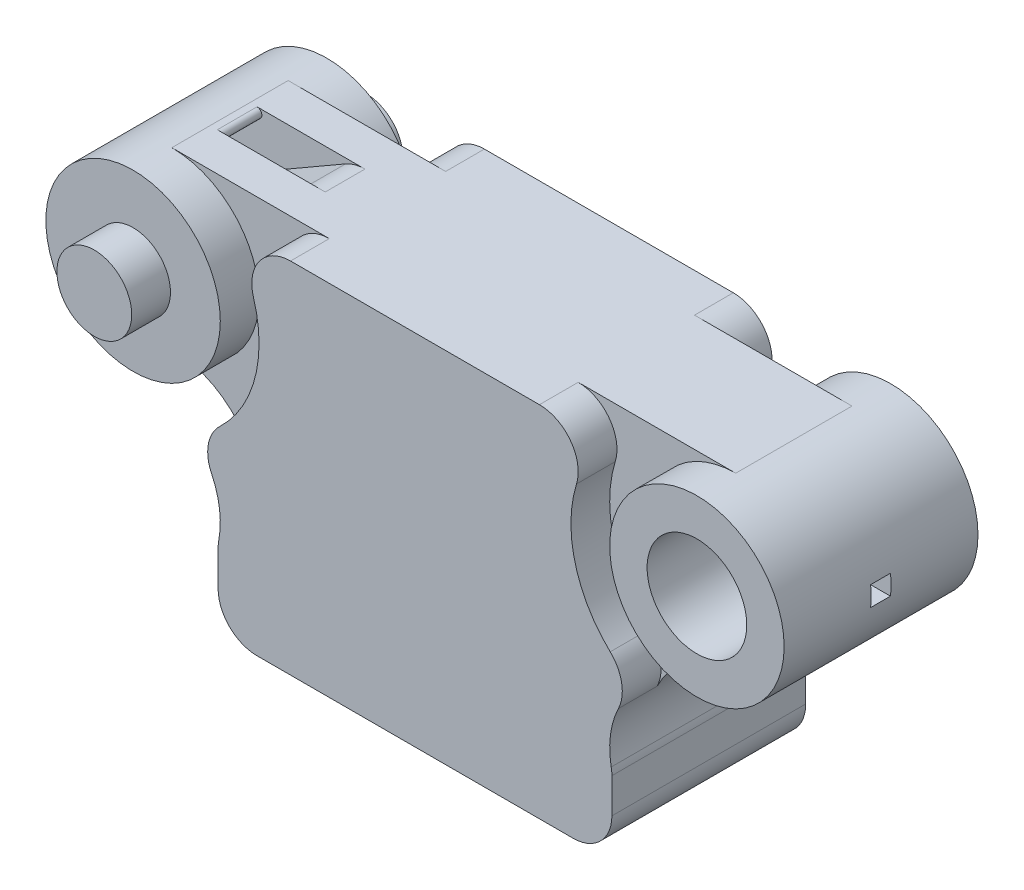
SolidWorks part; units mm, degrees
material "ABS"
ref_plane "Front Plane" through (0, 0, 0) normal (0, 0, 1) x (1, 0, 0)
ref_plane "Top Plane" through (0, 0, 0) normal (0, 1, 0) x (1, 0, 0)
ref_plane "Right Plane" through (0, 0, 0) normal (1, 0, 0) x (0, 0, -1)
sketch "Sketch1" plane through (0, 0, 0) normal (0, 0, 1) x (1, 0, 0)
  line L0 (5.5562, 0) -> (35.7188, 0)
  line L1 (0, 5.5562) -> (41.275, 5.5562)
  line L2 (0, 5.5562) -> (0, -5.5562) construction
  line L3 (0, -5.5562) -> (41.275, -5.5562) construction
  line L4 (41.275, 5.5562) -> (41.275, -5.5562) construction
  line L5 (0, 5.5562) -> (41.275, 5.5562) construction
  line L9 (0, 0) -> (9.0934, 0.7956) construction
  line L10 (41.275, 9.1281) -> (41.275, 0) construction
  line L11 (32.1816, 0.7956) -> (30.4025, 0.9512) construction
  line L12 (32.1816, 0.7956) -> (41.275, 0) construction
  line L13 (30.4025, 0.9512) -> (28.6233, 1.1069) construction
  circle A0 centre (0, 0) radius 5.5562 construction
  circle A1 centre (41.275, 0) radius 5.5562 construction
  arc A2 (0, 5.5562) -> (0, -5.5562) centre (0, 0) ccw
  arc A3 (41.275, -5.5562) -> (41.275, 5.5562) centre (41.275, 0) ccw
  circle A4 centre (0, 0) radius 1.7859
  circle A5 centre (41.275, 0) radius 1.7859
  arc A6 (0, -5.5562) -> (5.5562, 0) centre (0, 0) ccw
  arc A7 (35.7188, 0) -> (41.275, -5.5562) centre (41.275, 0) ccw
  circle A16 centre (41.275, -9.1281) radius 1.7859
  circle A20 centre (41.275, -9.1281) radius 3.5719
  circle A21 centre (32.1816, 0.7956) radius 1.7859
  circle A22 centre (32.1816, 0.7956) radius 3.5719 construction
  circle A23 centre (41.275, 0) radius 9.1281 construction
  circle A25 centre (0, 0) radius 9.1281 construction
  circle A40 centre (32.1816, 7.9393) radius 1.7859
  circle A41 centre (32.1816, 7.9393) radius 3.5719
  circle A42 centre (0, -9.1281) radius 3.5719
  circle A46 centre (9.0934, 0.7956) radius 1.7859
  circle A47 centre (9.0934, 7.9393) radius 1.7859
  circle A48 centre (9.0934, 7.9393) radius 3.5719
  circle A49 centre (9.0934, 0.7956) radius 3.5719 construction
  circle A50 centre (0, -9.1281) radius 1.7859
  arc A51 (0, -7.3422) -> (7.3142, 0.6399) centre (0, 0) ccw
  arc A52 (0, -10.9141) -> (10.8725, 0.9512) centre (0, 0) ccw
  arc A53 (0, -12.7) -> (12.6517, 1.1069) centre (0, 0) ccw
  arc A54 (28.6233, 1.1069) -> (41.275, -12.7) centre (41.275, 0) ccw
  arc A55 (30.4025, 0.9512) -> (41.275, -10.9141) centre (41.275, 0) ccw
  arc A56 (33.9608, 0.6399) -> (41.275, -7.3422) centre (41.275, 0) ccw
  dimension "D1" = 41.275
  dimension "D2" = 11.1125
  dimension "D3" = 3.5719
  dimension "D5" = 95
  dimension "D6" = 7.1438
  dimension "D7" = 3.5719
  dimension "D4" = 95
sketch "Sketch2" plane through (0, 0, 0) normal (0, 0, 1) x (1, 0, 0)
  line L0 (9.0934, 11.5112) -> (32.1816, 11.5112)
  line L1 (12.5755, 0) -> (28.6995, 0)
  line L2 (5.5562, 0) -> (35.7188, 0) construction
  line L3 (12.5755, 0) -> (12.5755, -3.175)
  line L4 (12.5755, -3.175) -> (28.6995, -3.175)
  line L5 (28.6995, -3.175) -> (28.6995, 0)
  circle A0 centre (32.1816, 0.7956) radius 3.5719
  circle A1 centre (9.0934, 0.7956) radius 3.5719
  circle A2 centre (9.0934, 7.9393) radius 3.5719
  circle A3 centre (32.1816, 7.9393) radius 3.5719
  circle A4 centre (9.0934, 7.9393) radius 3.5719 construction
  circle A5 centre (32.1816, 0.7956) radius 3.5719 construction
  circle A6 centre (9.0934, 0.7956) radius 3.5719 construction
  circle A7 centre (9.0934, 7.9393) radius 1.5319
  circle A8 centre (32.1816, 7.9393) radius 2.0399
  dimension "D2" = 3.0639
  dimension "D3" = 4.0799
  dimension "D1" = 3.175
extrude "Boss-Extrude1" add sketch "Sketch2" along normal blind 7.9375 contours A3 L0 A2 A1 L1 A0 | A2 A7 | A3 A8 | L4 L5 L1 L3 region at (20.6375, 5.814, 0) region at (11.5476, 10.3936, 0) region at (34.6359, 10.3936, 0) region at (20.6375, -1.5875, 0)
extrude "Boss-Extrude2" add sketch "Sketch2<3>" along normal blind 9.525 and the other way blind 1.5875 contours A7 region at (9.0934, 7.9393, 0)
sketch "Sketch2<3>" plane through (0, 0, 0) normal (0, 0, 1) x (1, 0, 0) same geometry as "Sketch2"
fillet "Fillet1" radius 1.5875 4 edges at (28.6995, 0, 3.9688) (28.6995, -3.175, 3.9688) (12.5755, -3.175, 3.9688) (12.5755, 0, 3.9688)
sketch "Sketch3" plane through (0, -3.175, 0) normal (0, -1, 0) x (-1, 0, 0)
  line L0 (-14.163, -3.9688) -> (-27.112, -3.9688) construction
  line L1 (-14.163, -7.9375) -> (-27.112, -7.9375) construction
  line L2 (-14.163, -7.9375) -> (-14.163, 0) construction
  line L3 (-14.163, 0) -> (-27.112, 0) construction
  line L4 (-27.112, -7.9375) -> (-27.112, 0) construction
  line L6 (-15.7505, -1.5875) -> (-17.338, -1.5875)
  line L7 (-15.7505, -1.5875) -> (-15.7505, -6.35)
  line L8 (-15.7505, -6.35) -> (-17.338, -6.35)
  line L9 (-17.338, -1.5875) -> (-17.338, -6.35)
  line L10 (-15.7505, -1.5875) -> (-17.338, -6.35) construction
  line L11 (-15.7505, -6.35) -> (-17.338, -1.5875) construction
  line L12 (-19.8437, -1.5875) -> (-21.4312, -1.5875)
  line L13 (-19.8437, -1.5875) -> (-19.8437, -6.35)
  line L14 (-19.8437, -6.35) -> (-21.4312, -6.35)
  line L15 (-21.4312, -1.5875) -> (-21.4312, -6.35)
  line L16 (-19.8437, -1.5875) -> (-21.4312, -6.35) construction
  line L17 (-19.8437, -6.35) -> (-21.4312, -1.5875) construction
  line L18 (-23.937, -1.5875) -> (-25.5245, -1.5875)
  line L19 (-23.937, -1.5875) -> (-23.937, -6.35)
  line L20 (-23.937, -6.35) -> (-25.5245, -6.35)
  line L21 (-25.5245, -1.5875) -> (-25.5245, -6.35)
  line L22 (-23.937, -1.5875) -> (-25.5245, -6.35) construction
  line L23 (-23.937, -6.35) -> (-25.5245, -1.5875) construction
  point P8 (-16.5443, -3.9688)
  point P13 (-20.6375, -3.9688)
  point P18 (-24.7307, -3.9688)
  dimension "D1" = 1.5875
  dimension "D2" = 1.5875
  dimension "D3" = 1.5875
  dimension "D4" = 4.7625
extrude "Cut-Extrude1" cut sketch "Sketch3" against normal blind 3.175
sketch "Sketch5" plane through (0, 0, 7.9375) normal (0, 0, 1) x (1, 0, 0)
  line L0 (5.5216, 7.9125) -> (35.7534, 7.9125) construction
  line L1 (9.0934, 11.5112) -> (32.1816, 11.5112) construction
  line L2 (5.5216, 7.9125) -> (11.7547, 11.5112) construction
  arc A0 (9.0934, 11.5112) -> (9.0934, 4.3674) centre (9.0934, 7.9393) ccw construction
  arc A1 (32.1816, 4.3674) -> (32.1816, 11.5112) centre (32.1816, 7.9393) ccw construction
  dimension "D1" = 3.5987
  dimension "D2" = 30
sketch3d "3DSketch1"
  line L2 (9.0934, 11.5112, 0) -> (32.1816, 11.5112, 0) construction
  line L3 (11.7547, 11.5112, 7.9375) -> (11.7547, 11.5112, 0) construction
sketch3d "3DSketch4"
  line L0 (11.7547, 11.5112, 7.9375) -> (11.7547, 11.5112, 0) construction
  line L1 (5.5216, 7.9125, 7.9375) -> (11.7547, 11.5112, 7.9375) construction
sketch3d "3DSketch6"
sketch "Sketch7" plane through (-2.0458, 3.5435, 0) normal (0.5, -0.866, 0) x (-0.866, -0.5, 0)
  line L0 (-8.7381, -7.9375) -> (-8.7381, 0) construction
  line L1 (-8.2729, 0) -> (-13.6307, 0) construction
ref_plane "Plane2" through (35.7535, 0, 0) normal (1, 0, 0) x (0, 0, -1)
sketch "Sketch8" plane through (7.5674, 4.3691, 0) normal (0.866, 0.5, 0) x (0, 0, -1)
  line L0 (-7.9375, 4.0916) -> (0, 4.0916) construction
  line L2 (-4.7816, 3.2788) -> (-3.156, 3.2788)
  line L3 (-4.7816, 3.2788) -> (-4.7816, 4.9044)
  line L4 (-4.7816, 4.9044) -> (-3.156, 4.9044)
  line L5 (-3.156, 3.2788) -> (-3.156, 4.9044)
  line L6 (-4.7816, 3.2788) -> (-3.156, 4.9044) construction
  line L7 (-4.7816, 4.9044) -> (-3.156, 3.2788) construction
  circle A0 centre (-3.9688, 4.0916) radius 0.8128 construction
  point P4 (-3.9688, 4.0916)
  dimension "D1" = 1.6256
extrude "Cut-Extrude2" cut sketch "Sketch8" against normal through all both and the other way through all
sketch "Sketch9" plane through (35.7535, 0, 0) normal (1, 0, 0) x (0, 0, -1)
  line L0 (-7.9375, 7.9393) -> (0, 7.9393) construction
  line L1 (-7.9375, 9.4713) -> (-7.9375, 6.4074) construction
  line L2 (0, 6.4074) -> (0, 9.4713) construction
  line L4 (-4.3751, 7.5329) -> (-3.5624, 7.5329)
  line L5 (-4.3751, 7.5329) -> (-4.3751, 8.3457)
  line L6 (-4.3751, 8.3457) -> (-3.5624, 8.3457)
  line L7 (-3.5624, 7.5329) -> (-3.5624, 8.3457)
  line L8 (-4.3751, 7.5329) -> (-3.5624, 8.3457) construction
  line L9 (-4.3751, 8.3457) -> (-3.5624, 7.5329) construction
  circle A0 centre (-3.9688, 7.9393) radius 0.4064 construction
  dimension "D1" = 0.8128
extrude "Cut-Extrude3" cut sketch "Sketch9" against normal blind 0.8928
sketch "Sketch10" plane through (0, 0, 7.9375) normal (0, 0, 1) x (1, 0, 0)
  line L0 (9.0934, 11.5112) -> (12.8164, 11.5112)
  line L1 (9.0934, 11.5112) -> (32.1816, 11.5112) construction
  line L2 (32.1816, 11.5112) -> (28.4586, 11.5112)
  circle A0 centre (9.0934, 7.9393) radius 3.5719
  circle A1 centre (9.0934, 7.9393) radius 5.1594
  circle A2 centre (32.1816, 7.9393) radius 3.5719
  circle A3 centre (32.1816, 7.9393) radius 5.1594
  arc A4 (32.1816, 4.3674) -> (32.1816, 11.5112) centre (32.1816, 7.9393) ccw construction
  arc A5 (32.1816, 4.3674) -> (28.6719, 0.1323) centre (32.1816, 0.7956) ccw construction
  arc A6 (12.6031, 0.1323) -> (9.0934, 4.3674) centre (9.0934, 0.7956) ccw construction
  arc A7 (32.1816, 4.3674) -> (29.7343, 3.3973) centre (32.1816, 0.7956) ccw
  arc A8 (11.5407, 3.3973) -> (9.0934, 4.3674) centre (9.0934, 0.7956) ccw
  arc M7 (28.6719, 0.1323) -> (32.1816, 4.3674) centre (32.1816, 0.7956) cw
  line M9 (32.1816, 11.5112) -> (9.0934, 11.5112)
  arc M11 (9.0934, 4.3674) -> (12.6031, 0.1323) centre (9.0934, 0.7956) cw
  dimension "D1" = 1.5875
  dimension "D2" = 1.5875
extrude "Cut-Extrude4" cut sketch "Sketch10" against normal blind 1.5875 contours A1 A0 M11 M9 | A3 A2 M9 M7 region at (10.9549, 11.415, 7.9375) region at (30.3201, 11.415, 7.9375)
extrude "Cut-Extrude5" cut sketch "Sketch10<3>" against normal blind 1.5875 from offset 6.35 contours A1 A0 M11 M9 | A3 A2 M9 M7 region at (10.9549, 11.415, 7.9375) region at (30.3201, 11.415, 7.9375) offset against normal yes
sketch "Sketch10<3>" plane through (0, 0, 7.9375) normal (0, 0, 1) x (1, 0, 0) same geometry as "Sketch10"
fillet "Fillet2" radius 1.5875 8 edges at (29.7343, 3.3973, 0.7938) (11.5407, 3.3973, 0.7938) (28.4586, 11.5112, 0.7938) (28.4586, 11.5112, 7.1437) (29.7343, 3.3973, 7.1437) (11.5407, 3.3973, 7.1437) (12.8164, 11.5112, 7.1437) (12.8164, 11.5112, 0.7938)
fillet "Fillet4" radius 1.5875 2 edges at (13.3803, 11.5112, 3.9688) (5.6365, 7.0403, 3.9688)
fillet "Fillet5" radius 0.1985 2 edges at (10.1291, 11.5112, 3.9688) (5.6623, 8.9323, 3.9688)
